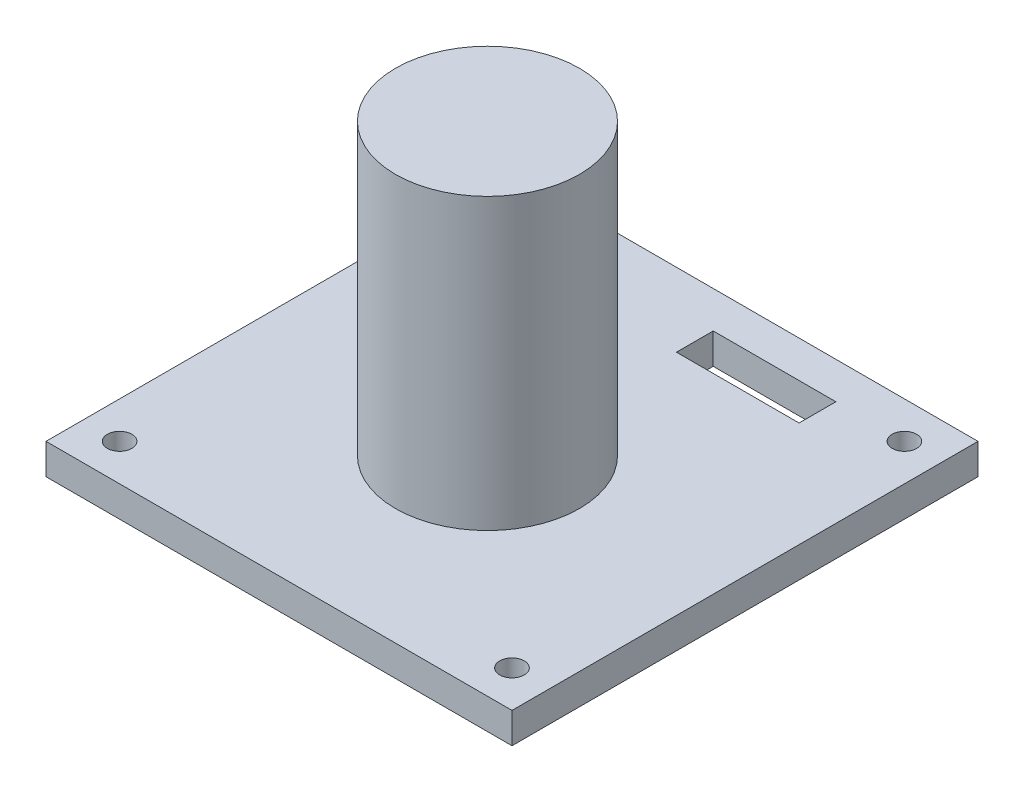
SolidWorks part; units mm, degrees
ref_plane "Front Plane" through (0, 0, 0) normal (0, 0, 1) x (1, 0, 0)
ref_plane "Top Plane" through (0, 0, 0) normal (0, 1, 0) x (1, 0, 0)
ref_plane "Right Plane" through (0, 0, 0) normal (1, 0, 0) x (0, 0, -1)
sketch "Sketch1" plane through (0, 0, 0) normal (0, 1, 0) x (1, 0, 0)
  line L0 (-19, 21) -> (-19, -17)
  line L1 (-19, -17) -> (19, -17)
  line L2 (19, -17) -> (19, 21)
  line L3 (19, 21) -> (-19, 21)
  line L4 (0.41, 18) -> (10.41, 18)
  line L5 (10.41, 18) -> (10.41, 15)
  line L6 (10.41, 15) -> (0.41, 15)
  line L7 (0.41, 15) -> (0.41, 18)
  circle A0 centre (0, 0) radius 7.5
  circle A1 centre (-16, 18) radius 1
  circle A2 centre (16, 18) radius 1
  circle A3 centre (16, -14) radius 1
  circle A4 centre (-16, -14) radius 1
  point P19 (0, 0)
  point P20 (0, 21)
  point P21 (0, 0)
  point P22 (0, 0)
  point P23 (0, 0)
  point P24 (0, 0)
  point P25 (0, 0)
  dimension "D2" = 3
  dimension "D3" = 3
  dimension "D4" = 15
  dimension "D5" = 2
  dimension "D8" = 3
  dimension "D1" = 38
  dimension "D6" = 10
  dimension "D7" = 29.41
  dimension "D9" = 3
  dimension "D10" = 3
extrude "Boss-Extrude1" add sketch "Sketch1" along normal blind 2.5 contours L2 L3 L0 L1 A4 A3 A2 A1 A0 L6 L7 L4 L5 region at (0, 0, -20.4626)
extrude "Boss-Extrude2" add sketch "Sketch1<6>" along normal blind 26.1 contours A0 region at (0, 0, 0)
sketch "Sketch1<6>" plane through (0, 0, 0) normal (0, 1, 0) x (1, 0, 0) same geometry as "Sketch1"
